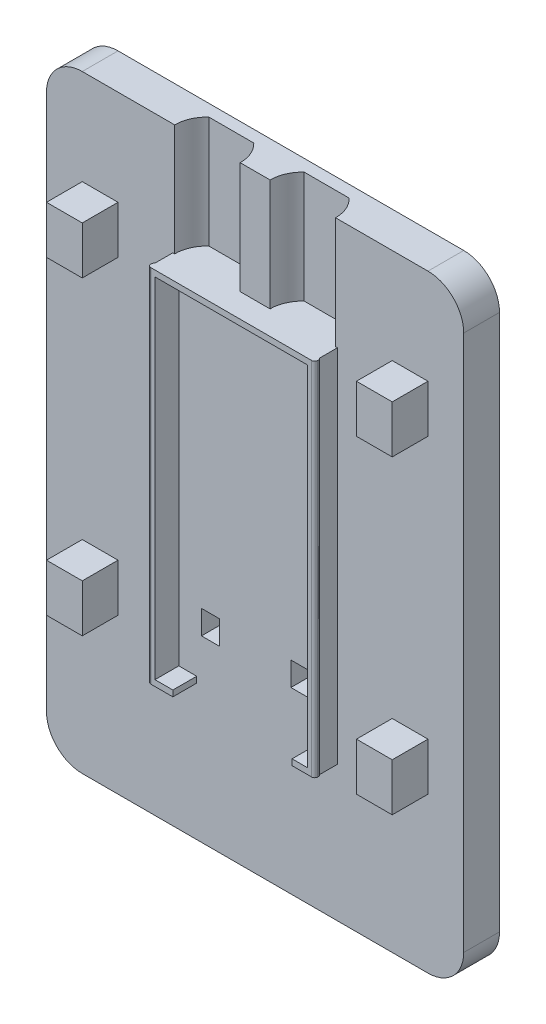
SolidWorks part; units mm, degrees
ref_plane "Front Plane" through (0, 0, 0) normal (0, 0, 1) x (1, 0, 0)
ref_plane "Top Plane" through (0, 0, 0) normal (0, 1, 0) x (1, 0, 0)
ref_plane "Right Plane" through (0, 0, 0) normal (1, 0, 0) x (0, 0, -1)
sketch "Sketch1" plane through (0, 0, 0) normal (0, 0, 1) x (1, 0, 0)
  line L1 (-15, 36) -> (0, 36)
  line L2 (-15, 36) -> (-15, 0)
  line L3 (-15, 0) -> (0, 0)
  line L4 (0, 36) -> (0, 0)
  dimension "D1" = 15
  dimension "D2" = 36
extrude "Boss-Extrude1" add sketch "Sketch1" along normal blind 2
sketch "Sketch2" plane through (0, 0, 2) normal (0, 0, 1) x (1, 0, 0)
  line L1 (-0.6, 1.37) -> (-14.4, 1.37)
  line L2 (-0.6, 1.37) -> (-0.6, 34.63)
  line L3 (-0.6, 34.63) -> (-14.4, 34.63)
  line L4 (-14.4, 1.37) -> (-14.4, 34.63)
  line L6 (0, 0) -> (0, 36) construction
  line L10 (-1.1, 1.87) -> (-13.9, 1.87)
  line L11 (-1.1, 1.87) -> (-1.1, 34.13)
  line L12 (-1.1, 34.13) -> (-13.9, 34.13)
  line L13 (-13.9, 1.87) -> (-13.9, 34.13)
  dimension "D1" = 13.8
  dimension "D2" = 0.6
  dimension "D3" = 33.26
  dimension "D4" = 0.5
extrude "Boss-Extrude2" add sketch "Sketch2" along normal blind 2
sketch "Sketch3" plane through (-14.4, 0, 0) normal (-1, 0, 0) x (0, 0, 1)
  line L0 (4, 34.63) -> (2, 34.63) construction
  line L1 (3.5, 34.63) -> (4, 34.63)
  line L2 (3.5, 34.63) -> (3.5, 1.37)
  line L3 (3.5, 1.37) -> (4, 1.37)
  line L4 (4, 34.63) -> (4, 1.37)
  line L5 (4, 1.37) -> (2, 1.37) construction
  line L6 (2, 34.63) -> (2, 1.37) construction
  dimension "D1" = 1.5
  dimension "D2" = 0.5
extrude "Boss-Extrude3" add sketch "Sketch3" along normal blind 0.1
fillet "Fillet1" radius 0.25 2 edges at (-14.5, 18, 4) (-14.5, 18, 3.5)
sketch "Sketch4" plane through (-0.6, 0, 0) normal (1, 0, 0) x (0, 0, -1)
  line L0 (-4, 34.63) -> (-2, 34.63) construction
  line L1 (-4, 1.37) -> (-3.5, 1.37)
  line L2 (-4, 1.37) -> (-4, 34.63)
  line L3 (-4, 34.63) -> (-3.5, 34.63)
  line L4 (-3.5, 1.37) -> (-3.5, 34.63)
  dimension "D1" = 0.5
extrude "Boss-Extrude4" add sketch "Sketch4" along normal blind 0.1
fillet "Fillet2" radius 0.25 2 edges at (-0.5, 18, 4) (-0.5, 18, 3.5)
sketch "Sketch5" plane through (0, 34.63, 0) normal (0, 1, 0) x (1, 0, 0)
  line L6 (-14.25, -4) -> (-0.75, -4)
  line L7 (-0.5, -3.75) -> (-0.5, -3.7)
  line L8 (-0.6, -3.5) -> (-0.6, -2)
  line L9 (-0.6, -2) -> (-14.4, -2)
  line L10 (-14.4, -2) -> (-14.4, -3.5)
  line L11 (-14.5, -3.7) -> (-14.5, -3.75)
  line L12 (-14.25, -4) -> (-0.75, -4)
  line L13 (-0.5, -3.75) -> (-0.5, -3.7)
  line L14 (-0.6, -3.5) -> (-0.6, -2)
  line L15 (-0.6, -2) -> (-14.4, -2)
  line L16 (-14.4, -2) -> (-14.4, -3.5)
  line L17 (-14.5, -3.7) -> (-14.5, -3.75)
  arc A4 (-0.75, -4) -> (-0.5, -3.75) centre (-0.75, -3.75) ccw
  arc A5 (-0.5, -3.7) -> (-0.6, -3.5) centre (-0.75, -3.7) ccw
  arc A6 (-14.4, -3.5) -> (-14.5, -3.7) centre (-14.25, -3.7) ccw
  arc A7 (-14.5, -3.75) -> (-14.25, -4) centre (-14.25, -3.75) ccw
  arc A8 (-0.75, -4) -> (-0.5, -3.75) centre (-0.75, -3.75) ccw
  arc A9 (-0.5, -3.7) -> (-0.6, -3.5) centre (-0.75, -3.7) ccw
  arc A10 (-14.4, -3.5) -> (-14.5, -3.7) centre (-14.25, -3.7) ccw
  arc A11 (-14.5, -3.75) -> (-14.25, -4) centre (-14.25, -3.75) ccw
  dimension "D1" = 0
extrude "Cut-Extrude1" cut sketch "Sketch5" against normal blind 3
sketch "Sketch6" plane through (-1.1, 0, 0) normal (-1, 0, 0) x (0, 0, 1)
  line L0 (2, 1.87) -> (2, 31.63) construction
  line L1 (4, 31.63) -> (2, 31.63)
  line L2 (4, 31.63) -> (4, 31.13)
  line L3 (4, 31.13) -> (2, 31.13)
  line L4 (2, 31.63) -> (2, 31.13)
  dimension "D1" = 0.5
extrude "Boss-Extrude5" add sketch "Sketch6" along normal up to next
sketch "Sketch7" plane through (0, 1.37, 0) normal (0, -1, 0) x (1, 0, 0)
  line L0 (-14.4, 3.5) -> (-14.4, 2) construction
  line L1 (-0.6, 3.5) -> (-14.4, 3.5)
  line L2 (-0.6, 3.5) -> (-0.6, 3)
  line L3 (-0.6, 3) -> (-14.4, 3)
  line L4 (-14.4, 3.5) -> (-14.4, 3)
  line L6 (-4.4, 3) -> (-10.4, 3)
  line L7 (-4.4, 3) -> (-4.4, 3.5)
  line L8 (-4.4, 3.5) -> (-10.4, 3.5)
  line L9 (-10.4, 3) -> (-10.4, 3.5)
  line L10 (-4.4, 3) -> (-10.4, 3.5) construction
  line L11 (-0.5, 3.7) -> (-0.5, 3.75)
  line L12 (-0.75, 4) -> (-14.25, 4)
  line L13 (-14.5, 3.75) -> (-14.5, 3.7)
  line L14 (-14.4, 3.5) -> (-14.4, 2)
  line L15 (-14.4, 2) -> (-0.6, 2)
  line L16 (-0.6, 2) -> (-0.6, 3.5)
  line L17 (-0.5, 3.7) -> (-0.5, 3.75)
  line L18 (-0.75, 4) -> (-14.25, 4)
  line L19 (-14.5, 3.75) -> (-14.5, 3.7)
  line L20 (-14.4, 3.5) -> (-14.4, 2)
  line L21 (-14.4, 2) -> (-0.6, 2)
  line L22 (-0.6, 2) -> (-0.6, 3.5)
  line L23 (-4.4, 3.5) -> (-10.4, 3) construction
  line L24 (-4.4, 3.5) -> (-10.4, 3.5)
  line L25 (-4.4, 3.5) -> (-4.4, 4)
  line L26 (-4.4, 4) -> (-10.4, 4)
  line L27 (-10.4, 3.5) -> (-10.4, 4)
  arc A4 (-0.5, 3.75) -> (-0.75, 4) centre (-0.75, 3.75) ccw
  arc A5 (-14.25, 4) -> (-14.5, 3.75) centre (-14.25, 3.75) ccw
  arc A6 (-14.5, 3.7) -> (-14.4, 3.5) centre (-14.25, 3.7) ccw
  arc A7 (-0.6, 3.5) -> (-0.5, 3.7) centre (-0.75, 3.7) ccw
  arc A8 (-0.5, 3.75) -> (-0.75, 4) centre (-0.75, 3.75) ccw
  arc A9 (-14.25, 4) -> (-14.5, 3.75) centre (-14.25, 3.75) ccw
  arc A10 (-14.5, 3.7) -> (-14.4, 3.5) centre (-14.25, 3.7) ccw
  arc A11 (-0.6, 3.5) -> (-0.5, 3.7) centre (-0.75, 3.7) ccw
  point P9 (-7.4, 3.25)
  dimension "D2" = 0.5
  dimension "D3" = 6
  dimension "D4" = 4
  dimension "D1" = 0
extrude "Cut-Extrude2" cut sketch "Sketch7" against normal blind 0.5 contours L27 L1 L25 L18 | L9 L3 L7 L1 region at (-7.4, 1.37, 3.25) region at (-7.4, 1.37, 3.75)
sketch "Sketch8" plane through (0, 0, 3) normal (0, 0, 1) x (1, 0, 0)
  line L4 (-10.4, 1.37) -> (-4.4, 1.37)
  line L5 (-4.4, 1.37) -> (-4.4, 1.87)
  line L6 (-4.4, 1.87) -> (-10.4, 1.87)
  line L7 (-10.4, 1.87) -> (-10.4, 1.37)
  line L8 (-10.4, 1.37) -> (-4.4, 1.37)
  line L9 (-4.4, 1.37) -> (-4.4, 1.87)
  line L10 (-4.4, 1.87) -> (-10.4, 1.87)
  line L11 (-10.4, 1.87) -> (-10.4, 1.37)
  dimension "D1" = 0
extrude "Cut-Extrude3" cut sketch "Sketch8" against normal up to surface (1 mm away) up to face at (-7.5, 18, 2)
sketch "Sketch10" plane through (0, 36, 0) normal (0, 1, 0) x (1, 0, 0)
  line L0 (0, -2) -> (-15, -2) construction
  line L2 (0, 0) -> (-0.5, 0)
  line L3 (-15, 0) -> (-14.5, 0)
  line L4 (-15, 0) -> (-15, -2)
  line L5 (-15, -2) -> (-14.5, -2)
  line L6 (-14.5, 0) -> (-14.5, -2)
  line L7 (0, 0) -> (0, -2)
  line L8 (0, -2) -> (-0.5, -2)
  line L9 (-0.5, 0) -> (-0.5, -2)
  line L13 (0, 0) -> (-15, 0)
  line L14 (-15, 0) -> (-15, -2)
  line L15 (-15, -2) -> (0, -2)
  line L16 (0, -2) -> (0, 0)
  line L17 (0, 0) -> (-15, 0)
  line L18 (-15, 0) -> (-15, -2)
  line L19 (-15, -2) -> (0, -2)
  line L20 (0, -2) -> (0, 0)
  arc A0 (-13.3875, 0) -> (-9.6125, 0) centre (-11.5, -2) ccw
  arc A1 (-5.3875, 0) -> (-1.6125, 0) centre (-3.5, -2) ccw
  dimension "D1" = 3
  dimension "D3" = 5.5
  dimension "D4" = 5.5
  dimension "D6" = 3
  dimension "D2" = 0.5
  dimension "D5" = 0.5
  dimension "D7" = 0
extrude "Cut-Extrude5" cut sketch "Sketch10" against normal up to surface (4.37 mm away) contours L19 A0 L17 | L19 A0 | L19 A1 L17 | L19 A1 region at (-3.5, 36, 1.0555) region at (-3.5, 36, 3.1671) region at (-11.5, 36, 1.0555) region at (-11.5, 36, 3.1671) up to face at (-7.5, 31.63, 3.398)
sketch "Sketch12" plane through (0, 0, 0) normal (0, 0, -1) x (-1, 0, 0)
  line L1 (15, 0) -> (0, 0)
  line L2 (15, 0) -> (15, 36)
  line L3 (15, 36) -> (0, 36)
  line L4 (0, 0) -> (0, 36)
extrude "Boss-Extrude7" add sketch "Sketch12" along normal blind 1
sketch "Sketch13" plane through (0, 0, -1) normal (0, 0, -1) x (-1, 0, 0)
  line L0 (15, 0) -> (15, 36) construction
  line L1 (0, 0) -> (15, 0)
  line L2 (0, 0) -> (0, 7)
  line L3 (0, 7) -> (15, 7)
  line L4 (15, 0) -> (15, 7)
  line L6 (4.5, 7) -> (3, 7)
  line L7 (4.5, 7) -> (4.5, 5)
  line L8 (4.5, 5) -> (3, 5)
  line L9 (3, 7) -> (3, 5)
  line L10 (10.5, 7) -> (12, 7)
  line L11 (10.5, 7) -> (10.5, 5)
  line L12 (10.5, 5) -> (12, 5)
  line L13 (12, 7) -> (12, 5)
  dimension "D1" = 7
  dimension "D2" = 1.5
  dimension "D3" = 2
  dimension "D4" = 9
  dimension "D5" = 2
  dimension "D6" = 1.5
  dimension "D7" = 3
extrude "Cut-Extrude6" cut sketch "Sketch13" against normal through all contours L3 L9 L8 L7 | L13 L3 L11 L12 region at (-3.75, 6, -1) region at (-11.25, 6, -1)
sketch "Sketch14" plane through (-15, 0, 0) normal (-1, 0, 0) x (0, 0, 1)
  line L4 (2, 36) -> (-1, 36)
  line L5 (-1, 36) -> (-1, 0)
  line L6 (-1, 0) -> (2, 0)
  line L7 (2, 0) -> (2, 36)
  line L8 (2, 36) -> (-1, 36)
  line L9 (-1, 36) -> (-1, 0)
  line L10 (-1, 0) -> (2, 0)
  line L11 (2, 0) -> (2, 36)
  dimension "D1" = 0
extrude "Boss-Extrude8" add sketch "Sketch14" along normal blind 10
sketch "Sketch15" plane through (0, 0, 0) normal (1, 0, 0) x (0, 0, -1)
  line L4 (-2, 0) -> (1, 0)
  line L5 (1, 0) -> (1, 36)
  line L6 (1, 36) -> (-2, 36)
  line L7 (-2, 36) -> (-2, 0)
  line L8 (-2, 0) -> (1, 0)
  line L9 (1, 0) -> (1, 36)
  line L10 (1, 36) -> (-2, 36)
  line L11 (-2, 36) -> (-2, 0)
  dimension "D1" = 0
extrude "Boss-Extrude9" add sketch "Sketch15" along normal blind 10
sketch "Sketch17" plane through (0, 1.37, 0) normal (0, -1, 0) x (1, 0, 0)
  line L0 (-4.4, 4) -> (-0.75, 4) construction
  line L1 (-4.4, 2) -> (-2.4, 2)
  line L2 (-4.4, 2) -> (-4.4, 4)
  line L3 (-4.4, 4) -> (-2.4, 4)
  line L4 (-2.4, 2) -> (-2.4, 4)
  line L5 (-14.25, 4) -> (-10.4, 4) construction
  line L6 (-10.4, 2) -> (-12.4, 2)
  line L7 (-10.4, 2) -> (-10.4, 4)
  line L8 (-10.4, 4) -> (-12.4, 4)
  line L9 (-12.4, 2) -> (-12.4, 4)
  dimension "D1" = 2
  dimension "D2" = 2
extrude "Cut-Extrude7" cut sketch "Sketch17" against normal blind 10
sketch "Sketch19" plane through (0, 0, -1) normal (0, 0, -1) x (-1, 0, 0)
  line L0 (25, 18) -> (-10, 18) construction
  line L1 (25, 36) -> (25, 0) construction
  line L2 (-10, 0) -> (-10, 36) construction
  text T0 "<b>MEKATRONIKA</b>"
extrude "Cut-Extrude8" cut sketch "Sketch19" against normal blind 2
sketch "Sketch20" plane through (0, 0, -1) normal (0, 0, -1) x (-1, 0, 0)
  line L0 (25, 22.7212) -> (-10, 22.7212) construction
  line L1 (25, 36) -> (25, 0) construction
  line L2 (-10, 0) -> (-10, 36) construction
  text T0 "<b>POLITEKNIK</b>"
extrude "Cut-Extrude9" cut sketch "Sketch20" against normal blind 2
sketch "Sketch21" plane through (0, 0, -1) normal (0, 0, -1) x (-1, 0, 0)
  line L0 (25, 27.3184) -> (-10, 27.3184) construction
  line L1 (25, 36) -> (25, 0) construction
  line L2 (-10, 0) -> (-10, 36) construction
  text T0 "<b>TAKUMI</b>"
extrude "Cut-Extrude10" cut sketch "Sketch21" against normal blind 2
sketch "Sketch22" plane through (0, 0, 2) normal (0, 0, 1) x (1, 0, 0)
  line L1 (-22, 33) -> (7, 33)
  line L2 (-22, 33) -> (-22, 3)
  line L3 (-22, 3) -> (7, 3)
  line L4 (7, 33) -> (7, 3)
  line L5 (-22, 33) -> (-19, 33)
  line L6 (-22, 33) -> (-22, 29)
  line L7 (-22, 29) -> (-19, 29)
  line L8 (-19, 33) -> (-19, 29)
  line L9 (7, 33) -> (4, 33)
  line L10 (7, 33) -> (7, 29)
  line L11 (7, 29) -> (4, 29)
  line L12 (4, 33) -> (4, 29)
  line L13 (-22, 3) -> (-19, 3)
  line L14 (-22, 3) -> (-22, 7)
  line L15 (-22, 7) -> (-19, 7)
  line L16 (-19, 3) -> (-19, 7)
  line L17 (7, 3) -> (4, 3)
  line L18 (7, 3) -> (7, 7)
  line L19 (7, 7) -> (4, 7)
  line L20 (4, 3) -> (4, 7)
  dimension "D1" = 3
  dimension "D2" = 4
  dimension "D3" = 4
  dimension "D4" = 3
  dimension "D5" = 3
  dimension "D6" = 4
  dimension "D7" = 3
  dimension "D8" = 4
extrude "Boss-Extrude10" add sketch "Sketch22" along normal blind 3 contours L8 L1 L2 L7 | L3 L16 L15 L2 | L20 L3 L4 L19 | L1 L12 L11 L4 region at (-20.5, 31, 2) region at (5.5, 31, 2) region at (-20.5, 5, 2) region at (5.5, 5, 2)
sketch "Sketch23" plane through (0, 36, 0) normal (0, 1, 0) x (1, 0, 0)
  line L8 (-0.75, -2) -> (10, -2)
  line L9 (10, -2) -> (10, 1)
  line L10 (10, 1) -> (-25, 1)
  line L11 (-25, 1) -> (-25, -2)
  line L12 (-25, -2) -> (-14.25, -2)
  line L13 (-13.3875, 0) -> (-9.6125, 0)
  line L14 (-8.75, -2) -> (-6.25, -2)
  line L15 (-5.3875, 0) -> (-1.6125, 0)
  line L16 (-0.75, -2) -> (10, -2)
  line L17 (10, -2) -> (10, 1)
  line L18 (10, 1) -> (-25, 1)
  line L19 (-25, 1) -> (-25, -2)
  line L20 (-25, -2) -> (-14.25, -2)
  line L21 (-13.3875, 0) -> (-9.6125, 0)
  line L22 (-8.75, -2) -> (-6.25, -2)
  line L23 (-5.3875, 0) -> (-1.6125, 0)
  arc A4 (-13.3875, 0) -> (-14.25, -2) centre (-11.5, -2) ccw
  arc A5 (-8.75, -2) -> (-9.6125, 0) centre (-11.5, -2) ccw
  arc A6 (-5.3875, 0) -> (-6.25, -2) centre (-3.5, -2) ccw
  arc A7 (-0.75, -2) -> (-1.6125, 0) centre (-3.5, -2) ccw
  arc A8 (-13.3875, 0) -> (-14.25, -2) centre (-11.5, -2) ccw
  arc A9 (-8.75, -2) -> (-9.6125, 0) centre (-11.5, -2) ccw
  arc A10 (-5.3875, 0) -> (-6.25, -2) centre (-3.5, -2) ccw
  arc A11 (-0.75, -2) -> (-1.6125, 0) centre (-3.5, -2) ccw
  dimension "D1" = 0
extrude "Boss-Extrude11" add sketch "Sketch23" along normal blind 5
fillet "Fillet3" radius 3 2 edges at (10, 41, 0.5) (-25, 41, 0.5)
sketch "Sketch24" plane through (0, 0, 0) normal (0, -1, 0) x (1, 0, 0)
  line L4 (10, 2) -> (-25, 2)
  line L5 (-25, 2) -> (-25, -1)
  line L6 (-25, -1) -> (10, -1)
  line L7 (10, -1) -> (10, 2)
  line L8 (10, 2) -> (-25, 2)
  line L9 (-25, 2) -> (-25, -1)
  line L10 (-25, -1) -> (10, -1)
  line L11 (10, -1) -> (10, 2)
  dimension "D1" = 0
extrude "Boss-Extrude12" add sketch "Sketch24" along normal blind 10
fillet "Fillet4" radius 3 2 edges at (-25, -10, 0.5) (10, -10, 0.5)
